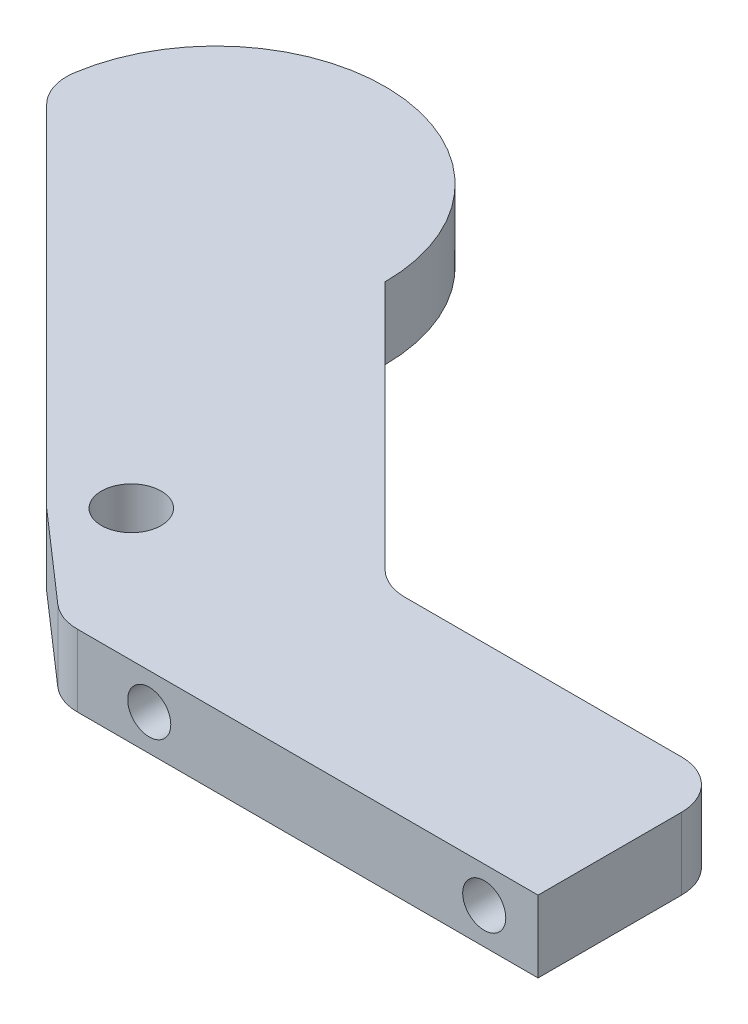
SolidWorks part; units mm, degrees
ref_plane "Front Plane" through (0, 0, 0) normal (0, 0, 1) x (1, 0, 0)
ref_plane "Top Plane" through (0, 0, 0) normal (0, 1, 0) x (1, 0, 0)
ref_plane "Right Plane" through (0, 0, 0) normal (1, 0, 0) x (0, 0, -1)
sketch "Sketch1" plane through (0, 0, 0) normal (0, 1, 0) x (1, 0, 0)
  line L0 (0, 6.35) -> (12.3665, 6.35)
  line L1 (12.3665, 6.35) -> (57.15, 6.35)
  line L2 (6.35, 0) -> (6.35, -13.97)
  line L3 (6.35, -13.97) -> (57.15, -13.97)
  line L4 (57.15, 6.35) -> (57.15, -13.97)
  line L5 (20.5908, 6.35) -> (-7.3492, 34.29)
  line L6 (-4.4901, -4.4901) -> (-43.2703, 34.29)
  line L7 (-4.4901, -4.4901) -> (6.35, -13.97)
  circle A0 centre (0, 0) radius 3.175
  arc A1 (0, 6.35) -> (6.35, 0) centre (0, 0) ccw
  arc A2 (-43.2703, 34.29) -> (-7.3492, 34.29) centre (-25.3097, 34.29) cw
  dimension "D1" = 12.7
  dimension "D2" = 6.35
  dimension "D3" = 6.35
  dimension "D4" = 50.8
  dimension "D5" = 20.32
  dimension "D6" = 45
  dimension "D7" = 25.4
  dimension "D8" = 27.94
extrude "Boss-Extrude1" add sketch "Sketch1" along normal mid plane 7.62 contours A2 L6 A1 L0 L1 L5 | L0 A1 L2 L3 L4 L1 A0 | A1 L7 L2 region at (-15.7867, 0, -26.7963) region at (28.8904, 0, 3.4247) region at (3.6646, 0, 8.0416)
sketch "Sketch2" plane through (0, 0, 13.97) normal (0, 0, 1) x (1, 0, 0)
  circle A0 centre (51.4379, 0) radius 1.8987 construction
  circle A1 centre (15.8779, 0) radius 1.8987 construction
  circle A2 centre (51.4379, 0) radius 1.8986
  circle A3 centre (15.8779, 0) radius 1.8986
  circle A4 centre (15.8779, 0) radius 2.286
  circle A5 centre (51.4379, 0) radius 2.286
  dimension "D1" = 4.572
  dimension "D2" = 4.572
extrude "Cut-Extrude1" cut sketch "Sketch2" against normal blind 5.08 contours A4 | A5 | A3 | A2 region at (51.4379, 0, 13.97) region at (15.8779, 0, 13.97) region at (13.6566, 0, 13.97) region at (49.2166, 0, 13.97)
fillet "Fillet1" radius 5.08 4 edges at (57.15, 0, -6.35) (20.5908, 0, -6.35) (6.35, 0, 13.97) (-43.2703, 0, -34.29)
